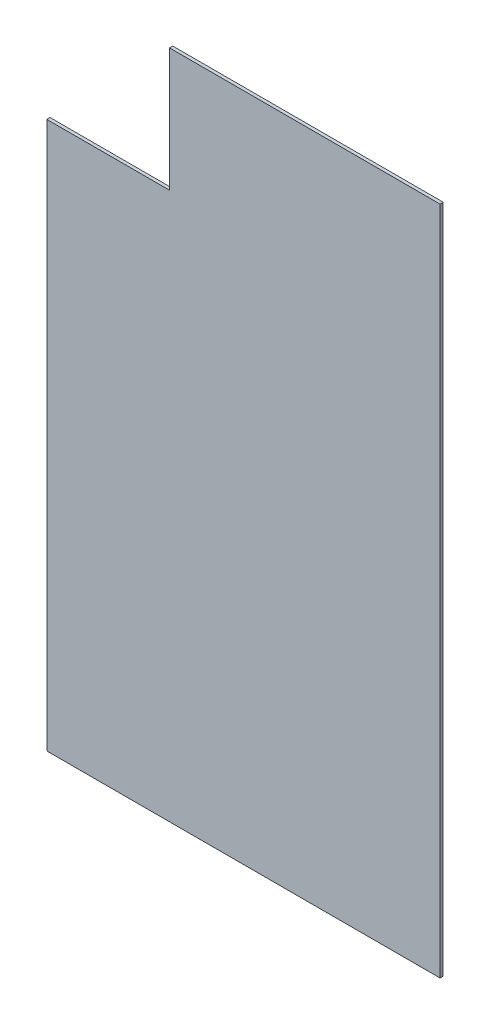
SolidWorks part; units mm, degrees
ref_plane "Ön Düzlem" through (0, 0, 0) normal (0, 0, 1) x (1, 0, 0)
ref_plane "Üst Düzlem" through (0, 0, 0) normal (0, 1, 0) x (1, 0, 0)
ref_plane "Sağ Düzlem" through (0, 0, 0) normal (1, 0, 0) x (0, 0, -1)
sketch "Çizim1" plane through (0, 0, 0) normal (0, 0, 1) x (1, 0, 0)
  line L0 (0, 0) -> (0, 2050)
  line L1 (0, 2050) -> (460, 2050)
  line L2 (460, 2050) -> (460, 2512)
  line L3 (460, 2512) -> (1474, 2512)
  line L4 (1474, 2512) -> (1474, 0)
  line L5 (1474, 0) -> (0, 0)
  dimension "D1" = 2050
  dimension "D2" = 460
  dimension "D3" = 462
  dimension "D4" = 1014
  dimension "D5" = 1474
  dimension "D6" = 2512
base flange "Taban-Flanş1" sketch "Çizim1" thickness 12 reverse thickness direction no parameters "D1"=5
sketch "Büküm-Çizgileri1" [suppressed] plane through (0, 0, 0) normal (0, 1, 0) x (1, 0, 0)
sketch "Sınırlandırma-Kutusu1" [suppressed] plane through (0, 0, 0) normal (0, 1, 0) x (1, 0, 0)
sheet metal parameters "Sac-Levha1" thickness 12 parameters "D1"=5
flat pattern "Düz-Çoğaltma1" [suppressed]
sketch "Büküm-Çizgileri2" plane through (0, 0, 0) normal (0, 1, 0) x (1, 0, 0)
sketch3d "Sınırlandırma-Kutusu2" [suppressed]
  line L0 (1474, 2512, 0) -> (1474, 0, 0) construction
  line L1 (0, 2512, 0) -> (0, 0, 0) construction
  line L2 (1474, 2512, 0) -> (0, 2512, 0) construction
  line L3 (1474, 0, 0) -> (0, 0, 0) construction
